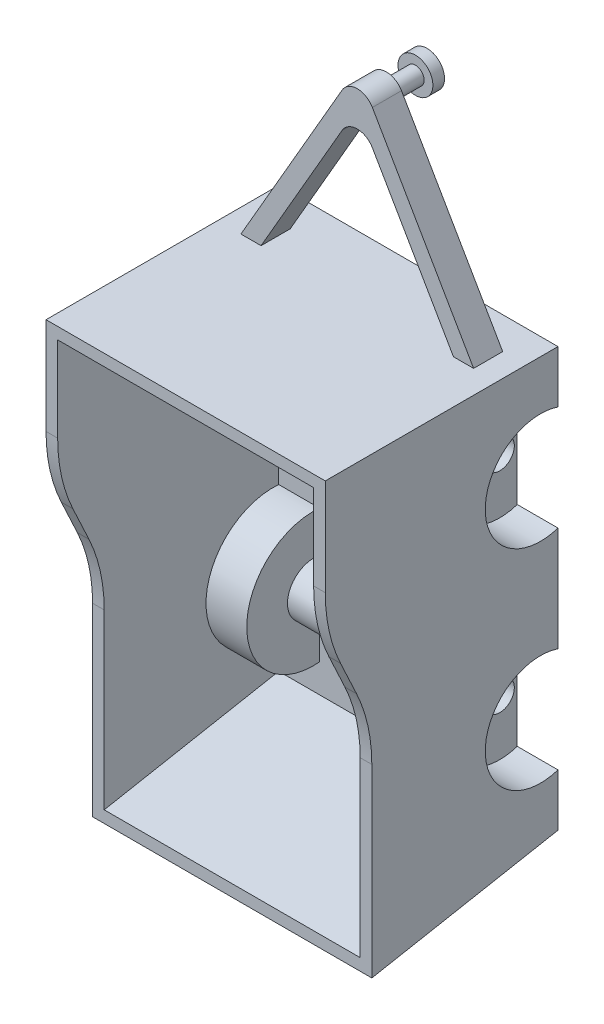
SolidWorks part; units mm, degrees
material "ABS"
ref_plane "Front Plane" through (0, 0, 0) normal (0, 0, 1) x (1, 0, 0)
ref_plane "Top Plane" through (0, 0, 0) normal (0, 1, 0) x (1, 0, 0)
ref_plane "Right Plane" through (0, 0, 0) normal (1, 0, 0) x (0, 0, -1)
sketch "Sketch1" plane through (0, 0, 0) normal (1, 0, 0) x (0, 0, -1)
  line L0 (0, 0) -> (-406.4, -76.2)
  line L1 (-406.4, -76.2) -> (-406.4, 406.4)
  line L2 (-406.4, 406.4) -> (-508, 624.2819)
  line L3 (-508, 624.2819) -> (-508, 914.4)
  line L4 (-508, 914.4) -> (0, 914.4)
  line L5 (0, 914.4) -> (0, 0)
  dimension "D1" = 508
  dimension "D2" = 406.4
  dimension "D3" = 914.4
  dimension "D4" = 990.6
  dimension "D5" = 0
  dimension "D6" = 0
  dimension "D7" = 155
  dimension "D8" = 482.6
extrude "Boss-Extrude1" add sketch "Sketch1" along normal blind 609.6
fillet "Fillet1" radius 355.6 2 edges at (304.8, 406.4, 406.4) (304.8, 624.2819, 508)
sketch "Sketch2" plane through (0, 0, 0) normal (-1, 0, 0) x (0, 0, 1)
  line L0 (0, 914.4) -> (508, 914.4) construction
  line L1 (38.1, 914.4) -> (38.1, -26.4379) construction
  line L2 (0, 0) -> (0, 914.4) construction
  line L3 (0, 457.2) -> (430.8713, 457.2) construction
  line L4 (0, 228.6) -> (406.4, 228.6) construction
  line L5 (406.4, 327.5654) -> (406.4, -76.2) construction
  arc A0 (439.717, 477.8484) -> (406.4, 327.5654) centre (762, 327.5654) ccw construction
  circle A1 centre (38.1, 228.6) radius 31.75
  circle A2 centre (38.1, 685.8) radius 31.75
  dimension "D4" = 63.5
  dimension "D1" = 940.8379
  dimension "D2" = 38.1
  dimension "D3" = 228.6
extrude "Cut-Extrude1" cut sketch "Sketch2" against normal blind 609.6
sketch "Sketch4" plane through (609.6, 0, 0) normal (1, 0, 0) x (0, 0, -1)
  line L0 (-38.1, 685.8) -> (120.9297, 685.8) construction
  circle A0 centre (-38.1, 685.8) radius 120.65
  dimension "D1" = 241.3
extrude "Cut-Extrude2" cut sketch "Sketch4" against normal blind 88.9 contours A0
ref_plane "Plane1" through (0, 457.2, 0) normal (0, 1, 0) x (1, 0, 0)
ref_plane "Plane2" through (304.8, 0, 0) normal (1, 0, 0) x (0, 0, -1)
mirror "Mirror1" about plane through (304.8, 0, 0) normal (1, 0, 0) of "Cut-Extrude2" second plane through (0, 457.2, 0) second plane normal (0, 1, 0)
shell "Shell1" thickness 25.4 removed face at (304.8, 808.7583, 508) removed face at (304.8, 627.0628, 495.4562) removed face at (304.8, 515.341, 457.2) removed face at (304.8, 403.6191, 418.9438) removed face at (304.8, 125.6827, 406.4)
sketch "Sketch6" plane through (0, 0, 0) normal (0, 0, -1) x (-1, 0, 0)
  line L0 (-558.8, 914.4) -> (-514.8059, 914.4)
  line L1 (-609.6, 914.4) -> (0, 914.4) construction
  line L2 (-94.7941, 914.4) -> (-50.8, 914.4)
  line L3 (-50.8, 914.4) -> (-271.8044, 1297.1909)
  line L5 (-558.8, 914.4) -> (-337.7956, 1297.1909)
  line L6 (-514.8059, 914.4) -> (-337.7956, 1220.9909)
  line L8 (-94.7941, 914.4) -> (-271.8044, 1220.9909)
  line L9 (-525.8044, 895.35) -> (-304.8, 1278.1409) construction
  line L10 (0, 876.3) -> (-72.797, 876.3) construction
  line L11 (0, 914.4) -> (-50.8, 914.4) construction
  line L12 (-72.797, 876.3) -> (-218.7432, 1129.0862) construction
  line L13 (-609.6, 800.2763) -> (-609.6, 914.4) construction
  line L14 (-218.7432, 1129.0862) -> (-304.8, 1278.1409) construction
  line L15 (-185.7477, 1148.1362) -> (-304.8, 1354.3409) construction
  line L16 (-50.8, 914.4) -> (-185.7477, 1148.1362) construction
  line L17 (-558.8, 914.4) -> (-304.8, 1354.3409) construction
  line L19 (-304.8, 1240.0409) -> (-254, 1228.2527) construction
  arc A0 (-271.8044, 1220.9909) -> (-337.7956, 1220.9909) centre (-304.8, 1201.9409) ccw
  arc A1 (-337.7956, 1297.1909) -> (-271.8044, 1297.1909) centre (-304.8, 1278.1409) cw
  dimension "D6" = 38.1
  dimension "D7" = 38.1
  dimension "D1" = 60
  dimension "D2" = 60
  dimension "D3" = 38.1
  dimension "D4" = 50.8
  dimension "D5" = 50.8
extrude "Boss-Extrude6" add sketch "Sketch6" against normal blind 63.5 from offset 69.85 offset against normal yes
sketch "Sketch8" plane through (0, 0, 69.85) normal (0, 0, -1) x (-1, 0, 0)
  line L0 (-304.8, 1240.0409) -> (-304.8, 1316.2409) construction
  arc A0 (-271.8044, 1220.9909) -> (-337.7956, 1220.9909) centre (-304.8, 1201.9409) ccw construction
  arc A1 (-271.8044, 1297.1909) -> (-337.7956, 1297.1909) centre (-304.8, 1278.1409) ccw construction
  circle A2 centre (-304.8, 1278.1409) radius 19.05
  dimension "D1" = 38.1
extrude "Boss-Extrude7" add sketch "Sketch8" along normal blind 63.5
sketch "Sketch9" plane through (0, 0, 6.35) normal (0, 0, -1) x (-1, 0, 0)
  circle A0 centre (-304.8, 1278.1409) radius 38.1
extrude "Boss-Extrude8" add sketch "Sketch9" along normal blind 25.4
